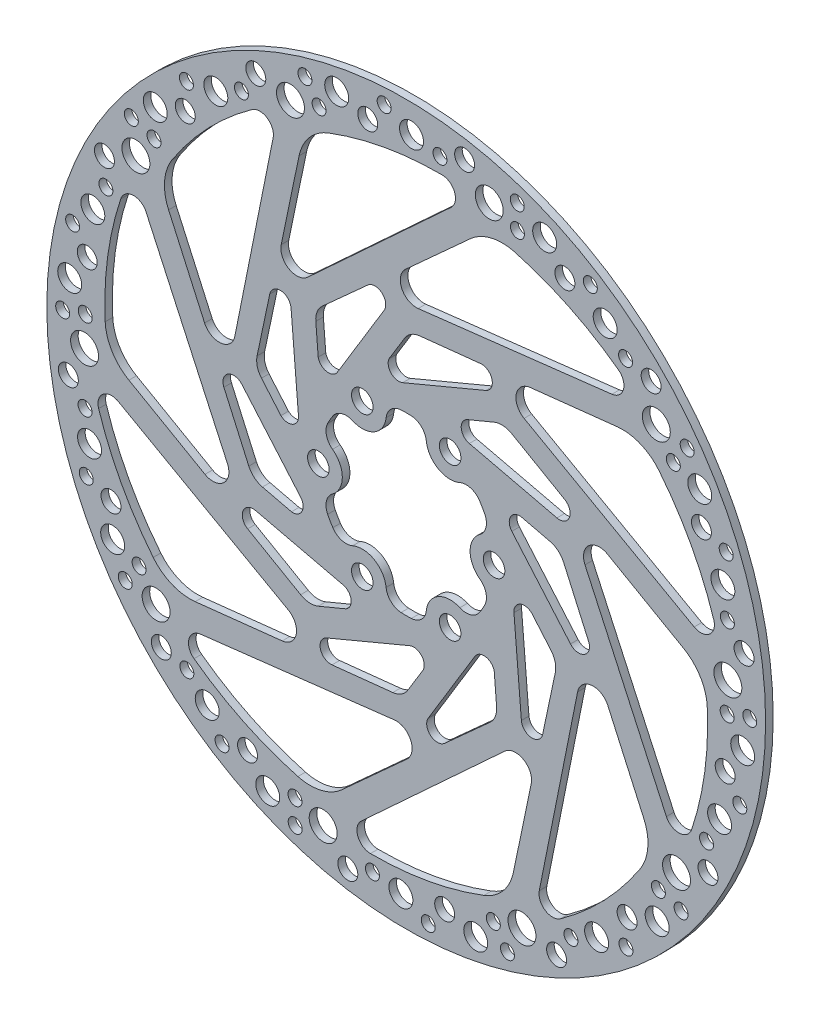
SolidWorks part; units mm, degrees
material "AISI Тип 316L нержавеющая сталь"
ref_plane "Front" through (0, 0, 0) normal (0, 0, 1) x (1, 0, 0)
ref_plane "Top" through (0, 0, 0) normal (0, 1, 0) x (1, 0, 0)
ref_plane "Right" through (0, 0, 0) normal (1, 0, 0) x (0, 0, -1)
sketch "Sketch1" plane through (0, 0, 0) normal (0, 0, 1) x (1, 0, 0)
  circle A0 centre (0, 0) radius 90
  dimension "D1" = 180
sketch "Sketch5" plane through (0, 0, 0) normal (0, 0, 1) x (1, 0, 0)
  circle A0 centre (0, 0) radius 90
  circle A1 centre (0, 0) radius 90 construction
extrude "Extrude2" add sketch "Sketch5" along normal blind 1.9
sketch "Sketch2" plane through (0, 0, 0) normal (0, 0, 1) x (1, 0, 0)
  line L0 (0, 0) -> (-11, 19.0526) construction
  line L1 (0, 0) -> (0, 22) construction
  line L2 (-21.0022, 34.6179) -> (-9.6329, 44.8759)
  line L3 (-5.5159, 41.4698) -> (-17.211, 22.2071)
  line L4 (-22.0393, 23.0436) -> (-22.6382, 30.5016)
  line L5 (11.2432, 72.1578) -> (-24.6773, 39.0489)
  line L6 (-31.3044, 42.8051) -> (-26.833, 64.2901)
  circle A2 centre (-11, 19.0526) radius 2.5 construction
  circle A3 centre (0, 0) radius 22 construction
  arc A4 (-9.6329, 44.8759) -> (-5.5159, 41.4698) centre (-7.824, 42.8711) cw
  arc A5 (-17.211, 22.2071) -> (-22.0393, 23.0436) centre (-19.4609, 23.5732) cw
  arc A6 (-22.6382, 30.5016) -> (-21.0022, 34.6179) centre (-17.6497, 30.9022) cw
  arc A7 (-24.6773, 39.0489) -> (-31.3044, 42.8051) centre (-27.3883, 41.9901) cw
  arc A8 (-26.833, 64.2901) -> (-19.4609, 72.9352) centre (-15.2513, 61.8797) cw
  arc A9 (11.2432, 72.1578) -> (8.9568, 78.068) centre (8.9349, 74.6622) ccw
  arc A10 (-19.4609, 72.9352) -> (8.9568, 78.068) centre (8.452, -0.3712) cw
  circle A11 centre (-28.9827, 75.2697) radius 3.5
  circle A12 centre (-17.4064, 82.9421) radius 3
  circle A13 centre (-25.3552, 82.2101) radius 1.75
  circle A14 centre (-21.8142, 77.4148) radius 1.75
  circle A15 centre (-9.6329, 80.8545) radius 2.5
  circle A16 centre (-5.5159, 86.0377) radius 1.75
  circle A17 centre (1.3302, 82.9421) radius 3
  circle A18 centre (8.452, 81.8174) radius 1.75
  circle A19 centre (14.6261, 84.2031) radius 2.5
  dimension "D1" = 44
  dimension "D2" = 5
  dimension "D4" = 7
  dimension "D5" = 3.5
  dimension "D6" = 6
  dimension "D7" = 5
  dimension "D3" = 30
extrude "Cut-Extrude5" cut sketch "Sketch2" along normal up to surface (1.9 mm away) up to face at (90, 0, 1.9)
pattern_circular "CirPattern3" count 10 over 360 about axis through (0, 0, 1.9) along (0, 0, -1) of "Cut-Extrude5"
sketch "Sketch4" plane through (0, 0, 0) normal (0, 0, 1) x (1, 0, 0)
  line L0 (-11, 19.0526) -> (0, 0) construction
  line L1 (0, 22) -> (0, 0) construction
  line L2 (0, 0) -> (-19.0526, 11) construction
  line L3 (-9.5263, 5.5) -> (0, 11) construction
  arc A0 (-13.4192, 13.5619) -> (-5.0353, 18.4023) centre (-11, 19.0526) ccw
  arc A1 (-18.3725, 12.1018) -> (-19.0526, 11) centre (0, 0) ccw
  circle A2 centre (0, 0) radius 22 construction
  arc A3 (-13.4192, 13.5619) -> (-18.3725, 12.1018) centre (-15.032, 9.9014) ccw
  arc A4 (-5.0353, 18.4023) -> (-1.2942, 21.9619) centre (-1.0589, 17.9688) cw
  arc A5 (0, 22) -> (-1.2942, 21.9619) centre (0, 0) ccw
  arc A6 (5.0353, 18.4023) -> (13.4192, 13.5619) centre (11, 19.0526) ccw
  arc A7 (13.4192, 13.5619) -> (18.3725, 12.1018) centre (15.032, 9.9014) cw
  arc A8 (19.0526, 11) -> (18.3725, 12.1018) centre (0, 0) ccw
  arc A9 (5.0353, 18.4023) -> (1.2942, 21.9619) centre (1.0589, 17.9688) ccw
  arc A10 (1.2942, 21.9619) -> (0, 22) centre (0, 0) ccw
  arc A11 (18.4545, 4.8404) -> (18.4545, -4.8404) centre (22, 0) ccw
  arc A12 (18.4545, -4.8404) -> (19.6667, -9.8601) centre (16.0909, -8.0674) cw
  arc A13 (19.0526, -11) -> (19.6667, -9.8601) centre (0, 0) ccw
  arc A14 (18.4545, 4.8404) -> (19.6667, 9.8601) centre (16.0909, 8.0674) ccw
  arc A15 (19.6667, 9.8601) -> (19.0526, 11) centre (0, 0) ccw
  arc A16 (13.4192, -13.5619) -> (5.0353, -18.4023) centre (11, -19.0526) ccw
  arc A17 (5.0353, -18.4023) -> (1.2942, -21.9619) centre (1.0589, -17.9688) cw
  arc A18 (0, -22) -> (1.2942, -21.9619) centre (0, 0) ccw
  arc A19 (13.4192, -13.5619) -> (18.3725, -12.1018) centre (15.032, -9.9014) ccw
  arc A20 (18.3725, -12.1018) -> (19.0526, -11) centre (0, 0) ccw
  arc A21 (-5.0353, -18.4023) -> (-13.4192, -13.5619) centre (-11, -19.0526) ccw
  arc A22 (-13.4192, -13.5619) -> (-18.3725, -12.1018) centre (-15.032, -9.9014) cw
  arc A23 (-19.0526, -11) -> (-18.3725, -12.1018) centre (0, 0) ccw
  arc A24 (-5.0353, -18.4023) -> (-1.2942, -21.9619) centre (-1.0589, -17.9688) ccw
  arc A25 (-1.2942, -21.9619) -> (0, -22) centre (0, 0) ccw
  arc A26 (-18.4545, -4.8404) -> (-18.4545, 4.8404) centre (-22, 0) ccw
  arc A27 (-18.4545, 4.8404) -> (-19.6667, 9.8601) centre (-16.0909, 8.0674) cw
  arc A28 (-19.0526, 11) -> (-19.6667, 9.8601) centre (0, 0) ccw
  arc A29 (-18.4545, -4.8404) -> (-19.6667, -9.8601) centre (-16.0909, -8.0674) ccw
  arc A30 (-19.6667, -9.8601) -> (-19.0526, -11) centre (0, 0) ccw
  point P17 (-4.7631, 8.25)
  dimension "D1" = 12
  dimension "D2" = 4
extrude "Cut-Extrude6" cut sketch "Sketch4" along normal up to surface (1.9 mm away) up to face at (-39.5032, 71.1596, 1.9)
hole_wizard "Ø5.4 (5.4) Diameter Hole1" positions "Sketch7" profile "Sketch6" hole size "Ø5.4" standard "BSI"
sketch "Sketch7" plane through (0, 0, 0) normal (0, 0, -1) x (-1, 0, 0)
  point P0 (11, 19.0526)
sketch "Sketch6" plane through (-11, 19.0526, 0) normal (1, 0, 0) x (0, 1, 0)
  line L0 (0, 0) -> (0, 6.6223)
  line L1 (0, 6.6223) -> (2.7, 5)
  line L2 (2.7, 5) -> (2.7, 0)
  line L5 (2.7, 0) -> (0, 0)
  line L10 (0, 6.6223) -> (-2.7, 5) construction
  line L11 (0, -6.35) -> (0, 107.95) construction
  dimension "Hole Dia." = 5.4
  dimension "Hole Depth" = 5
  dimension "Drill Angle" = 118
pattern_circular "CirPattern4" count 6 over 360 about axis through (0, 0, 1.9) along (0, 0, -1) of "Ø5.4 (5.4) Diameter Hole1"
